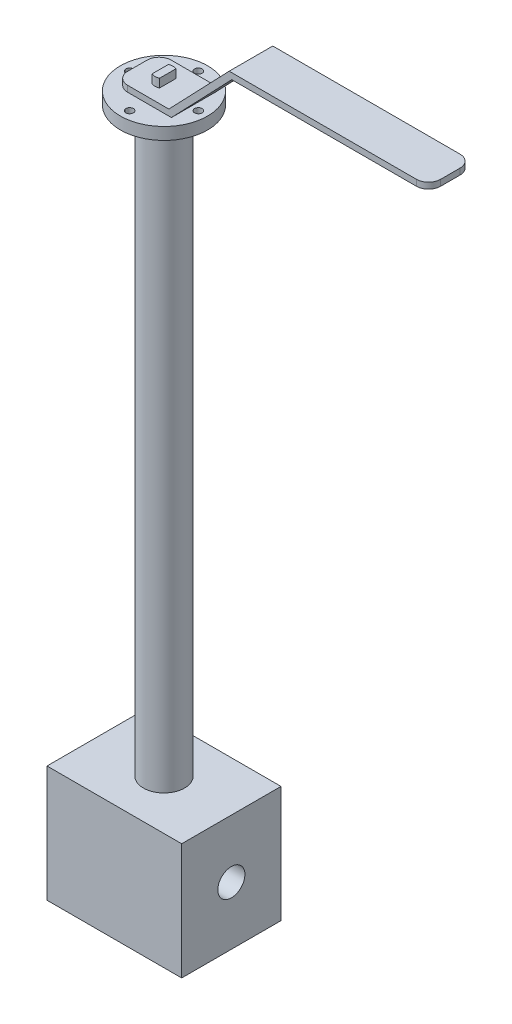
SolidWorks part; units mm, degrees
ref_plane "Front Plane" through (0, 0, 0) normal (0, 0, 1) x (1, 0, 0)
ref_plane "Top Plane" through (0, 0, 0) normal (0, 1, 0) x (1, 0, 0)
ref_plane "Right Plane" through (0, 0, 0) normal (1, 0, 0) x (0, 0, -1)
sketch "Sketch1" plane through (0, 0, 0) normal (0, 1, 0) x (1, 0, 0)
  circle A0 centre (0, 0) radius 22.86
  dimension "D1" = 45.72
extrude "Boss-Extrude1" add sketch "Sketch1" along normal blind 6.35
sketch "Sketch2" plane through (0, 6.35, 0) normal (0, 1, 0) x (1, 0, 0)
  line L0 (1.9685, 4.2668) -> (1.9685, -4.2668)
  line L1 (-1.9685, 4.2668) -> (-1.9685, -4.2668)
  line L2 (0, 0) -> (1.9685, 0) construction
  line L3 (0, 0) -> (-1.9685, 0) construction
  circle A0 centre (0, 0) radius 4.699
  dimension "D1" = 9.398
  dimension "D2" = 1.9685
  dimension "D3" = 1.9685
extrude "Boss-Extrude2" add sketch "Sketch2" along normal blind 8.89 contours L0 A0 L1 region at (0, 6.35, 0)
sketch "Sketch3" plane through (0, 0, 0) normal (0, -1, 0) x (1, 0, 0)
  circle A0 centre (0, 0) radius 10.795
  dimension "D1" = 21.59
extrude "Boss-Extrude3" add sketch "Sketch3" along normal blind 304.8
chamfer "Chamfer1" distance 3.81 angle 45 1 edges at (0, 0, -10.795)
sketch "Sketch4" plane through (0, 6.35, 0) normal (0, 1, 0) x (1, 0, 0)
  line L0 (0, 0) -> (0, 18) construction
  circle A0 centre (0, 0) radius 18 construction
  dimension "D1" = 36
hole_wizard "5/32 (0.15625) Diameter Hole1" positions "Sketch5" profile "Sketch6" hole size "5/32" standard "ANSI Inch" end condition up to next
sketch "Sketch5" plane through (0, 6.35, 0) normal (0, 1, 0) x (1, 0, 0)
  point P0 (0, 18)
sketch "Sketch6" plane through (0, 6.35, -18) normal (1, 0, 0) x (0, 0, 1)
  line L0 (0, 0) -> (0, 6.351)
  line L1 (0, 6.351) -> (1.9844, 6.351)
  line L2 (1.9844, 6.351) -> (1.9844, 0)
  line L5 (1.9844, 0) -> (0, 0)
  line L11 (0, -6.35) -> (0, 107.95) construction
  dimension "Thru Hole Dia." = 3.9688
  dimension "Thru Hole Depth" = 6.351
pattern_circular "CirPattern1" count 4 over 360 about axis through (0, 6.35, 0) along (0, 1, 0) of "5/32 (0.15625) Diameter Hole1"
sketch "Sketch7" plane through (0, -304.8, 0) normal (0, -1, 0) x (1, 0, 0)
  line L0 (-35.306, 26.035) -> (35.306, -26.035) construction
  line L1 (-35.306, 26.035) -> (35.306, 26.035)
  line L2 (-35.306, 26.035) -> (-35.306, -26.035)
  line L3 (-35.306, -26.035) -> (35.306, -26.035)
  line L4 (35.306, 26.035) -> (35.306, -26.035)
  point P4 (0, 0)
  dimension "D1" = 52.07
  dimension "D2" = 70.612
extrude "Boss-Extrude4" add sketch "Sketch7" along normal blind 60.96
sketch "Sketch8" plane through (35.306, 0, 0) normal (1, 0, 0) x (0, 0, -1)
  line L0 (-26.035, -304.8) -> (26.035, -365.76) construction
  circle A0 centre (0, -335.28) radius 7.112
  dimension "D1" = 14.224
extrude "Cut-Extrude1" cut sketch "Sketch8" against normal through all
sketch "Sketch9" plane through (0, 0, 0) normal (0, 0, 1) x (1, 0, 0)
  line L0 (-13.97, 7.62) -> (15.3255, 7.62)
  line L1 (15.3255, 7.62) -> (46.9483, 40.64)
  line L2 (46.9483, 40.64) -> (150.114, 40.64)
  line L3 (150.114, 40.64) -> (150.114, 43.815)
  line L4 (150.114, 43.815) -> (45.5927, 43.815)
  line L5 (45.5927, 43.815) -> (13.97, 10.795)
  line L6 (13.97, 10.795) -> (-13.97, 10.795)
  line L7 (-13.97, 10.795) -> (-13.97, 7.62)
  line L8 (-1.9685, 10.795) -> (1.9685, 10.795) construction
  line L9 (-1.9685, 15.24) -> (-1.9685, 6.35) construction
  line L10 (1.9685, 15.24) -> (1.9685, 6.35) construction
  point P14 (0, 10.795)
  point P15 (0, 10.795)
  dimension "D1" = 33.02
  dimension "D2" = 3.175
  dimension "D3" = 3.175
  dimension "D4" = 3.175
  dimension "D5" = 150.114
  dimension "D6" = 45.72
  dimension "D7" = 27.94
extrude "Boss-Extrude5" add sketch "Sketch9" along normal mid plane 22.86
fillet "Fillet1" radius 6.35 4 edges at (-13.97, 9.2075, 11.43) (-13.97, 9.2075, -11.43) (150.114, 42.2275, 11.43) (150.114, 42.2275, -11.43)
equation "\"D2@Sketch2\"=(.37-.215)/2"
